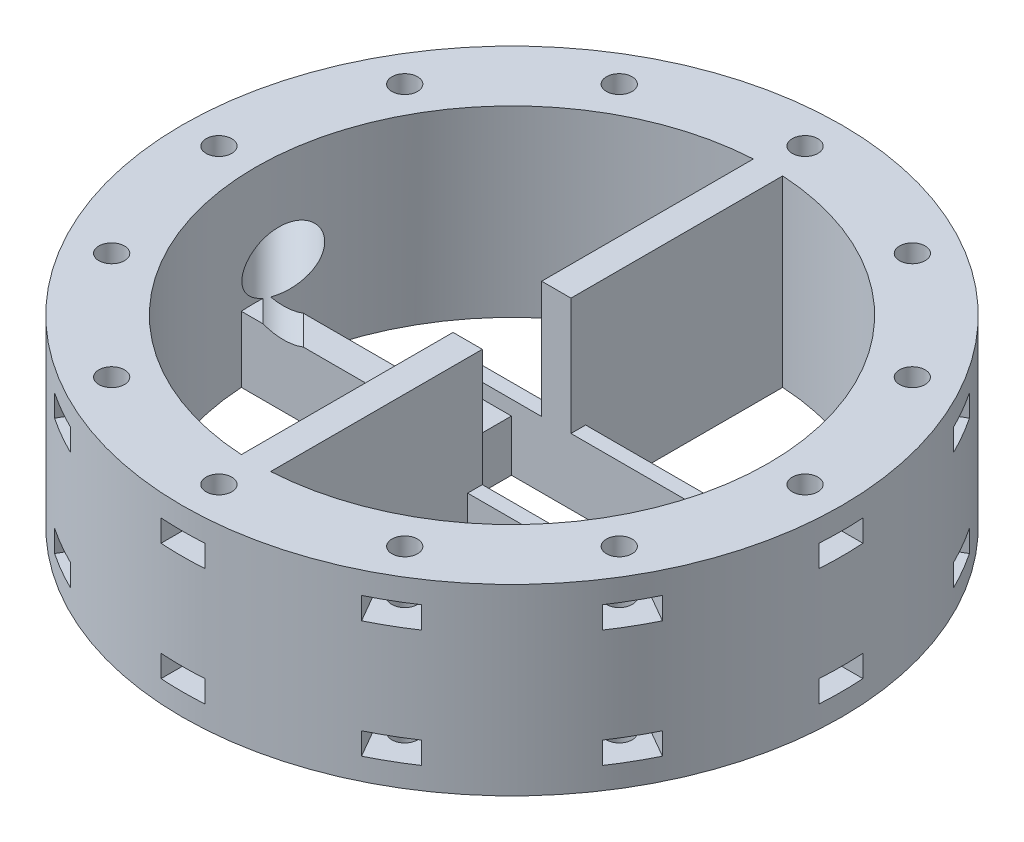
SolidWorks part; units mm, degrees
ref_plane "Front Plane" through (0, 0, 0) normal (0, 0, 1) x (1, 0, 0)
ref_plane "Top Plane" through (0, 0, 0) normal (0, 1, 0) x (1, 0, 0)
ref_plane "Right Plane" through (0, 0, 0) normal (1, 0, 0) x (0, 0, -1)
sketch "Sketch2" plane through (0, 0, 0) normal (0, 1, 0) x (1, 0, 0)
  line L0 (0, 0) -> (0, 45) construction
  circle A0 centre (0, 0) radius 45
  dimension "D1" = 90
extrude "Boss-Extrude1" add sketch "Sketch2" along normal blind 9
sketch "Sketch3" plane through (0, 9, 0) normal (0, 1, 0) x (1, 0, 0)
  line L0 (0, 45) -> (0, 0) construction
  line L1 (0, 0) -> (45, 0) construction
  line L2 (-10.95, 6.05) -> (21.3, 6.05)
  line L3 (21.3, 6.05) -> (21.3, -6.05)
  line L4 (-10.95, 6.05) -> (-10.95, -6.05)
  line L5 (-10.95, -6.05) -> (21.3, -6.05)
  circle A0 centre (0, 0) radius 45 construction
  point P12 (21.3, 0)
  point P13 (-10.95, 0)
  dimension "D1" = 32.25
  dimension "D2" = 10.95
  dimension "D3" = 12.1
extrude "Cut-Extrude1" cut sketch "Sketch3" against normal blind 2
sketch "Sketch4" plane through (0, 7, 0) normal (0, 1, 0) x (1, 0, 0)
  line L0 (5.175, 6.05) -> (5.175, -6.05) construction
  line L1 (21.3, 6.05) -> (-10.95, 6.05) construction
  line L2 (-10.95, -6.05) -> (21.3, -6.05) construction
  line L4 (-6.125, 6.05) -> (16.475, 6.05)
  line L5 (-6.125, 6.05) -> (-6.125, -6.05)
  line L6 (-6.125, -6.05) -> (16.475, -6.05)
  line L7 (16.475, 6.05) -> (16.475, -6.05)
  line L8 (-6.125, 6.05) -> (16.475, -6.05) construction
  line L9 (-6.125, -6.05) -> (16.475, 6.05) construction
  point P6 (5.175, 0)
  dimension "D1" = 22.6
extrude "Cut-Extrude2" cut sketch "Sketch4" against normal through all
sketch "Sketch6" plane through (0, 7, 0) normal (0, 1, 0) x (1, 0, 0)
  line L0 (-10.95, 0) -> (21.3, 0) construction
  line L1 (-10.95, 6.05) -> (-10.95, -6.05) construction
  line L2 (21.3, -6.05) -> (21.3, 6.05) construction
  line L3 (5.175, 6.05) -> (5.175, -6.05) construction
  line L4 (21.3, 6.05) -> (-10.95, 6.05) construction
  line L5 (-10.95, -6.05) -> (21.3, -6.05) construction
  circle A0 centre (-8.675, 0) radius 1
  circle A1 centre (19.025, 0) radius 1
  dimension "D1" = 2
  dimension "D2" = 27.7
extrude "Cut-Extrude4" cut sketch "Sketch6" against normal through all
sketch "Sketch9" plane through (0, 9, 0) normal (0, 1, 0) x (1, 0, 0)
  line L0 (-10.95, 6.05) -> (-10.95, -6.05) construction
  line L1 (-12.95, 8.05) -> (-2, 8.05)
  line L2 (-12.95, 8.05) -> (-12.95, 2)
  line L3 (-12.95, -8.05) -> (-2, -8.05)
  line L4 (-12.95, 2) -> (-34.9428, 2)
  line L6 (21.3, 6.05) -> (-10.95, 6.05) construction
  line L7 (0, 0) -> (-31.825, 0) construction
  line L8 (0, 0) -> (0, 31.7606) construction
  line L9 (-2, 34.9428) -> (-2, 8.05)
  line L10 (2, 34.9428) -> (2, 8.05)
  line L11 (-12.95, -2) -> (-34.9428, -2)
  line L12 (2, -34.9428) -> (2, -8.05)
  line L13 (-2, -34.9428) -> (-2, -8.05)
  line L14 (-12.95, -2) -> (-12.95, -8.05)
  line L15 (2, 8.05) -> (34.0617, 8.05)
  line L16 (2, -8.05) -> (34.0617, -8.05)
  arc A0 (34.0617, 8.05) -> (2, 34.9428) centre (0, 0) ccw
  arc A1 (-34.9428, -2) -> (-2, -34.9428) centre (0, 0) ccw
  arc A2 (-2, 34.9428) -> (-34.9428, 2) centre (0, 0) ccw
  arc A3 (2, -34.9428) -> (34.0617, -8.05) centre (0, 0) ccw
  dimension "D1" = 70
  dimension "D2" = 2
  dimension "D4" = 2
  dimension "D5" = 4
  dimension "D6" = 4
extrude "Cut-Extrude5" cut sketch "Sketch9" against normal through all
sketch "Sketch10" plane through (0, 0, 0) normal (0, -1, 0) x (1, 0, 0)
  circle A0 centre (0, 0) radius 40 construction
  circle A1 centre (-40, 0) radius 1.75
  circle A2 centre (-34.641, 20) radius 1.75
  circle A3 centre (-20, 34.641) radius 1.75
  circle A4 centre (0, 40) radius 1.75
  circle A5 centre (20, 34.641) radius 1.75
  circle A6 centre (34.641, 20) radius 1.75
  circle A7 centre (40, 0) radius 1.75
  circle A8 centre (34.641, -20) radius 1.75
  circle A9 centre (20, -34.641) radius 1.75
  circle A10 centre (0, -40) radius 1.75
  circle A11 centre (-20, -34.641) radius 1.75
  circle A12 centre (-34.641, -20) radius 1.75
  point P29 (0, 0)
  dimension "D1" = 80
  dimension "D2" = 3.5
  dimension "D3" = 12
sketch "Sketch13" plane through (0, 9, 0) normal (0, 1, 0) x (1, 0, 0)
  line L0 (2, -34.9428) -> (2, -8.05)
  line L1 (2, 6.05) -> (2, 34.9428)
  line L2 (-2, -8.05) -> (-2, -34.9428)
  line L3 (2, 6.05) -> (-2, 6.05)
  line L5 (2, -6.05) -> (-2, -6.05)
  line L6 (-2, 34.9428) -> (-2, 6.05)
  line L8 (2, -8.05) -> (2, -6.05)
  line L9 (-2, -6.05) -> (-2, -8.05)
  circle A0 centre (0, 0) radius 45
  arc A1 (34.9857, 1) -> (2, 34.9428) centre (0, 0) ccw
  arc A2 (-2, 34.9428) -> (-34.9428, 2) centre (0, 0) ccw
  arc A3 (-34.9428, 2) -> (-2, -34.9428) centre (0, 0) ccw
  arc A4 (2, -34.9428) -> (34.9857, 1) centre (0, 0) ccw
  dimension "D1" = 90
extrude "Boss-Extrude2" add sketch "Sketch13" along normal blind 16
extrude "Cut-Extrude7" cut sketch "Sketch10" against normal through all
ref_plane "Plane1" through (0, 22, 0) normal (0, 1, 0) x (1, 0, 0)
sketch "Sketch14" plane through (0, 22, 0) normal (0, 1, 0) x (1, 0, 0)
  line L0 (31.641, -18.2679) -> (31.641, -21.7321)
  line L1 (36.5359, 0) -> (38.2679, -3)
  line L2 (38.2679, -3) -> (44.8999, -3)
  line L3 (34.641, -16.5359) -> (31.641, -18.2679)
  line L4 (40.3844, -19.8519) -> (34.641, -16.5359)
  line L5 (44.8999, 3) -> (38.2679, 3)
  line L6 (38.2679, 3) -> (36.5359, 0)
  line L7 (43.4641, 0) -> (42.5981, 1.5) [skipped]
  line L8 (41.7321, -3) -> (42.5981, -1.5) [skipped]
  line L9 (31.641, -21.7321) -> (37.3844, -25.048)
  line L10 (18.2679, -31.641) -> (16.5359, -34.641)
  line L11 (21.7321, -31.641) -> (18.2679, -31.641)
  line L12 (25.048, -37.3844) -> (21.7321, -31.641)
  line L13 (16.5359, -34.641) -> (19.8519, -40.3844)
  line L14 (0, -36.5359) -> (-3, -38.2679)
  line L15 (3, -38.2679) -> (0, -36.5359)
  line L16 (3, -44.8999) -> (3, -38.2679)
  line L17 (-3, -38.2679) -> (-3, -44.8999)
  line L18 (-18.2679, -31.641) -> (-21.7321, -31.641)
  line L19 (-16.5359, -34.641) -> (-18.2679, -31.641)
  line L20 (-19.8519, -40.3844) -> (-16.5359, -34.641)
  line L21 (-21.7321, -31.641) -> (-25.048, -37.3844)
  line L22 (-31.641, -18.2679) -> (-34.641, -16.5359)
  line L23 (-31.641, -21.7321) -> (-31.641, -18.2679)
  line L24 (-37.3844, -25.048) -> (-31.641, -21.7321)
  line L25 (-34.641, -16.5359) -> (-40.3844, -19.8519)
  line L26 (-36.5359, 0) -> (-38.2679, 3)
  line L27 (-38.2679, -3) -> (-36.5359, 0)
  line L28 (-44.8999, -3) -> (-38.2679, -3)
  line L29 (-38.2679, 3) -> (-44.8999, 3)
  line L30 (-31.641, 18.2679) -> (-31.641, 21.7321)
  line L31 (-34.641, 16.5359) -> (-31.641, 18.2679)
  line L32 (-40.3844, 19.8519) -> (-34.641, 16.5359)
  line L33 (-31.641, 21.7321) -> (-37.3844, 25.048)
  line L34 (-18.2679, 31.641) -> (-16.5359, 34.641)
  line L35 (-21.7321, 31.641) -> (-18.2679, 31.641)
  line L36 (-25.048, 37.3844) -> (-21.7321, 31.641)
  line L37 (-16.5359, 34.641) -> (-19.8519, 40.3844)
  line L38 (0, 36.5359) -> (3, 38.2679)
  line L39 (-3, 38.2679) -> (0, 36.5359)
  line L40 (-3, 44.8999) -> (-3, 38.2679)
  line L41 (3, 38.2679) -> (3, 44.8999)
  line L42 (18.2679, 31.641) -> (21.7321, 31.641)
  line L43 (16.5359, 34.641) -> (18.2679, 31.641)
  line L44 (19.8519, 40.3844) -> (16.5359, 34.641)
  line L45 (21.7321, 31.641) -> (25.048, 37.3844)
  line L46 (31.641, 18.2679) -> (34.641, 16.5359)
  line L47 (31.641, 21.7321) -> (31.641, 18.2679)
  line L48 (37.3844, 25.048) -> (31.641, 21.7321)
  line L49 (34.641, 16.5359) -> (40.3844, 19.8519)
  circle A0 centre (40, 0) radius 3 construction
  arc A1 (44.8999, -3) -> (44.8999, 3) centre (0, 0) ccw
  arc A2 (37.3844, -25.048) -> (40.3844, -19.8519) centre (0, 0) ccw
  arc A3 (19.8519, -40.3844) -> (25.048, -37.3844) centre (0, 0) ccw
  arc A4 (-3, -44.8999) -> (3, -44.8999) centre (0, 0) ccw
  arc A5 (-25.048, -37.3844) -> (-19.8519, -40.3844) centre (0, 0) ccw
  arc A6 (-40.3844, -19.8519) -> (-37.3844, -25.048) centre (0, 0) ccw
  arc A7 (-44.8999, 3) -> (-44.8999, -3) centre (0, 0) ccw
  arc A8 (-37.3844, 25.048) -> (-40.3844, 19.8519) centre (0, 0) ccw
  arc A9 (-19.8519, 40.3844) -> (-25.048, 37.3844) centre (0, 0) ccw
  arc A10 (3, 44.8999) -> (-3, 44.8999) centre (0, 0) ccw
  arc A11 (25.048, 37.3844) -> (19.8519, 40.3844) centre (0, 0) ccw
  arc A12 (40.3844, 19.8519) -> (37.3844, 25.048) centre (0, 0) ccw
  point P71 (0, 0)
  dimension "D1" = 6
  dimension "D2" = 12
extrude "Cut-Extrude8" cut sketch "Sketch14" against normal blind 3
ref_plane "Plane2" through (0, 12.5, 0) normal (0, 1, 0) x (1, 0, 0)
mirror "Mirror1" about plane through (0, 12.5, 0) normal (0, 1, 0) of "Cut-Extrude8"
ref_plane "Plane3" through (0, 0, 0) normal (-0.7071, 0, -0.7071) x (-0.7071, 0, 0.7071)
sketch "Sketch15" plane through (0, 0, 0) normal (-0.7071, 0, -0.7071) x (-0.7071, 0, 0.7071)
  line L1 (14.5187, 19) -> (29.6277, 19) construction
  line L2 (14.5187, 6) -> (29.6277, 6) construction
  line L3 (22.0732, 19) -> (22.0732, 6) construction
  circle A0 centre (22.0732, 12.5) radius 4
  dimension "D1" = 8
extrude "Cut-Extrude9" cut sketch "Sketch15" along normal through all
